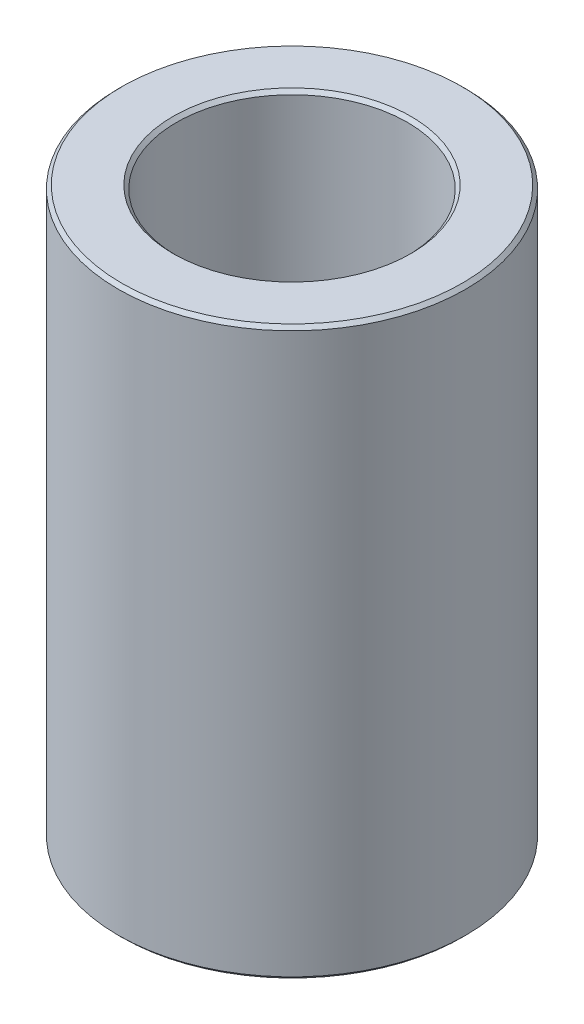
SolidWorks part; units mm, degrees
ref_plane "Front Plane" through (0, 0, 0) normal (0, 0, 1) x (1, 0, 0)
ref_plane "Top Plane" through (0, 0, 0) normal (0, 1, 0) x (1, 0, 0)
ref_plane "Right Plane" through (0, 0, 0) normal (1, 0, 0) x (0, 0, -1)
sketch "Sketch1" plane through (0, 0, 0) normal (0, 1, 0) x (1, 0, 0)
  circle A0 centre (0, 0) radius 52.5
  dimension "SLEEVE_OD" = 105
extrude "Boss-Extrude1" add sketch "Sketch1" along normal blind 171.2157
sketch "Sketch2" plane through (0, 0, 0) normal (0, 1, 0) x (1, 0, 0)
  circle A0 centre (0, 0) radius 34.8982
  dimension "BORE_D" = 69.7964
extrude "Cut-Extrude1" cut sketch "Sketch2" along normal through all
chamfer "Chamfer1" distance 1.05 angle 45 4 edges at (0, 171.2157, 34.8982) (0, 0, 34.8982) (0, 0, 52.5) (0, 171.2157, 52.5)
